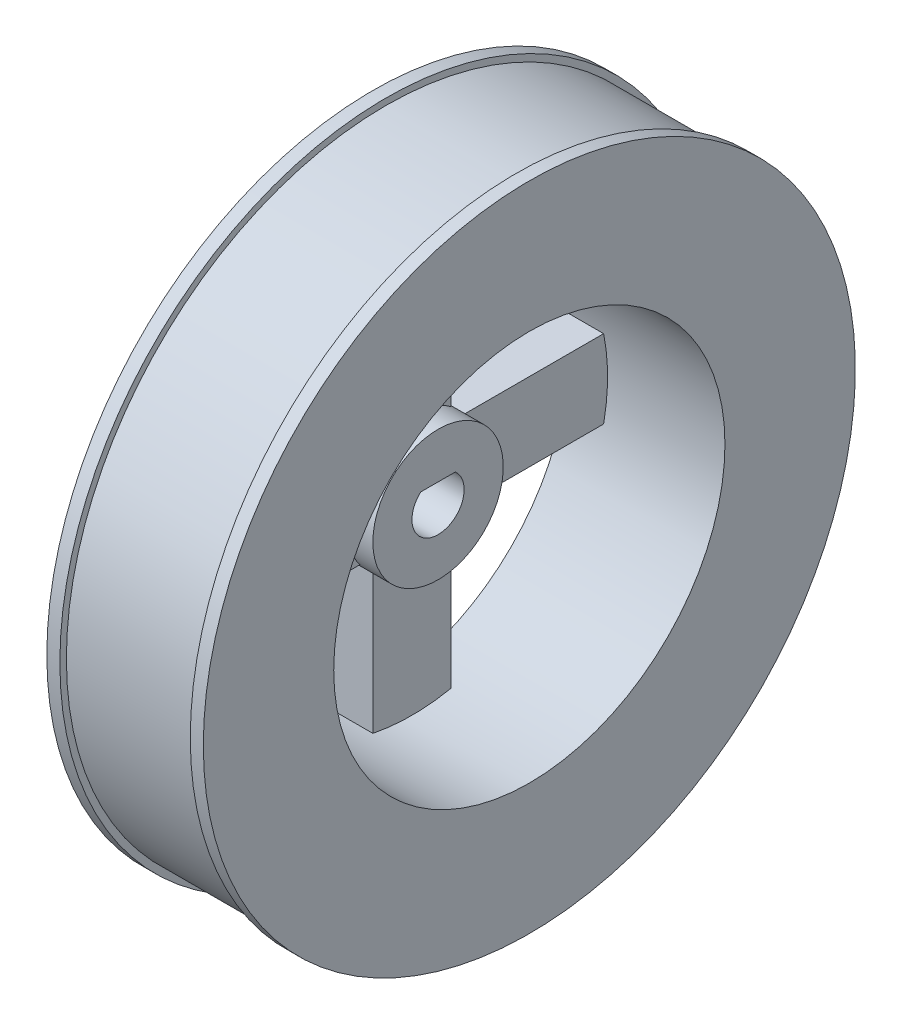
SolidWorks part; units mm, degrees
ref_plane "Front Plane" through (0, 0, 0) normal (0, 0, 1) x (1, 0, 0)
ref_plane "Top Plane" through (0, 0, 0) normal (0, 1, 0) x (1, 0, 0)
ref_plane "Right Plane" through (0, 0, 0) normal (1, 0, 0) x (0, 0, -1)
sketch "Sketch1" plane through (0, 0, 0) normal (0, 0, 1) x (1, 0, 0)
  line L0 (0, 0) -> (41532.2986, 0) construction
  line L1 (-6, 25) -> (-6, 15)
  line L3 (6, 15) -> (6, 25)
  line L4 (6, 25) -> (5, 25)
  line L5 (5, 25) -> (5, 24.5)
  line L6 (5, 24.5) -> (-5, 24.5)
  line L7 (-5, 24.5) -> (-5, 25)
  line L8 (-5, 25) -> (-6, 25)
  line L9 (-6, 15) -> (6, 15)
  line L10 (-1, 5) -> (-6, 5)
  line L11 (-6, 5) -> (-6, 0)
  line L12 (-6, 0) -> (-1, 0)
  line L13 (-1, 0) -> (-1, 5)
  point P9 (0, 0)
  point P15 (0, 15)
  point P18 (0, 0)
  dimension "D1" = 50
  dimension "D2" = 0.5
  dimension "D3" = 1
  dimension "D4" = 10
  dimension "D5" = 10
  dimension "D6" = 10
  dimension "D7" = 5
revolve "Revolve1" add sketch "Sketch1" angle 360 about L0
sketch "Sketch2" plane through (-6, 0, 0) normal (1, 0, 0) x (0, 0, -1)
  line L2 (0, 0) -> (0, 50000) construction
  line L9 (-3, 4) -> (-3, 14.6969)
  line L10 (3, 4) -> (3, 14.6969)
  arc A0 (-3, 14.6969) -> (3, 14.6969) centre (0, 0) cw
  circle A12 centre (0, 0) radius 15 construction
  circle A13 centre (0, 0) radius 5
  arc A14 (3, 4) -> (-3, 4) centre (0, 0) ccw
  dimension "D2" = 6
  dimension "D3" = 0
extrude "Boss-Extrude1" add sketch "Sketch2" along normal blind 3
sketch "Sketch3" plane through (-1, 0, 0) normal (1, 0, 0) x (0, 0, -1)
  line L0 (-1.3229, 1.5) -> (1.3229, 1.5)
  arc A0 (-1.3229, 1.5) -> (1.3229, 1.5) centre (0, 0) ccw
  dimension "D1" = 4
  dimension "D2" = 1.5
extrude "Cut-Extrude1" cut sketch "Sketch3" against normal through all both and the other way through all
pattern_circular "CirPattern1" count 4 over 360 about axis through (-6, 0, 0) along (1, 0, 0) of "Boss-Extrude1" reverse direction yes
